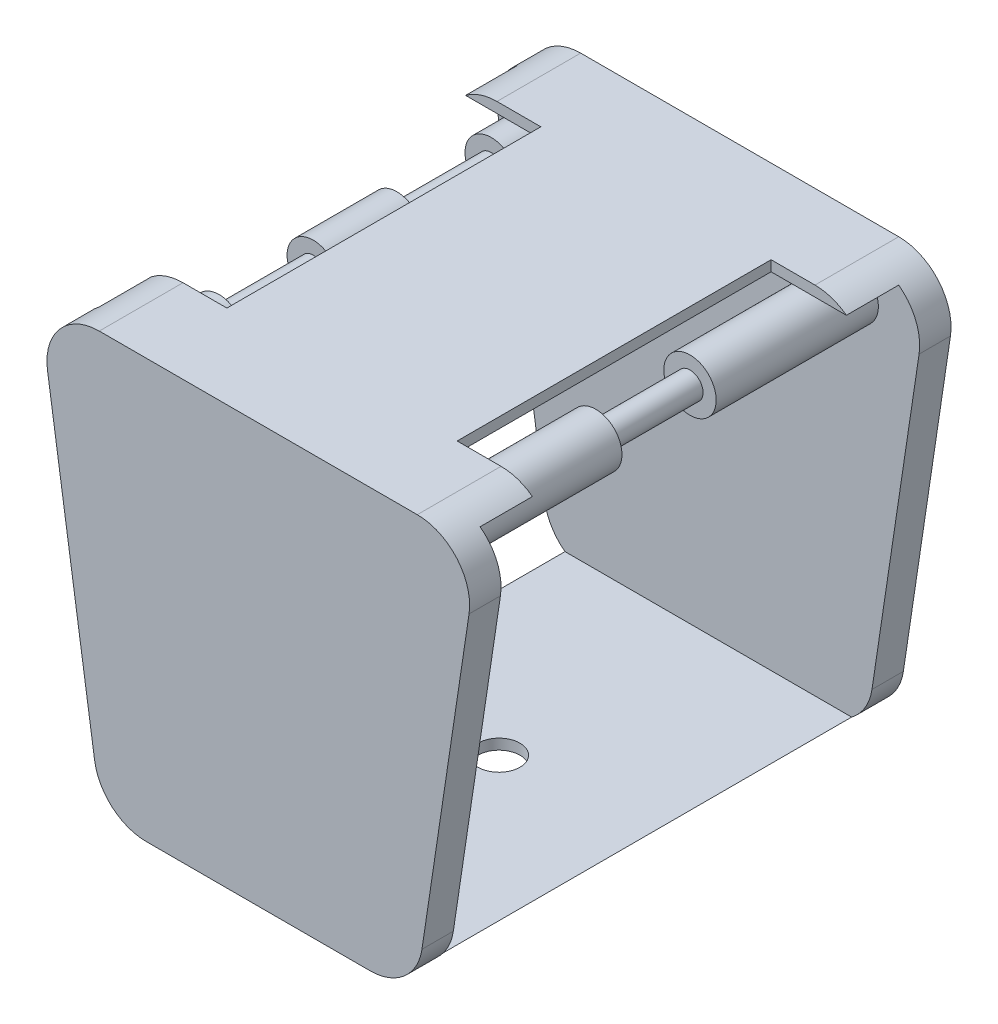
SolidWorks part; units mm, degrees
ref_plane "Front Plane" through (0, 0, 0) normal (0, 0, 1) x (1, 0, 0)
ref_plane "Top Plane" through (0, 0, 0) normal (0, 1, 0) x (1, 0, 0)
ref_plane "Right Plane" through (0, 0, 0) normal (1, 0, 0) x (0, 0, -1)
sketch "Sketch3" plane through (0, 0, 0) normal (0, 0, 1) x (1, 0, 0)
  line L0 (42, 40) -> (-42, 40)
  line L1 (-42, 40) -> (-30, -40)
  line L2 (-30, -40) -> (30, -40)
  line L3 (30, -40) -> (42, 40)
  line L4 (55, 0) -> (-55, 0) construction
  line L5 (0, -55) -> (0, 55) construction
  dimension "D1" = 84
  dimension "D2" = 60
  dimension "D3" = 80
  dimension "D4" = 40
  dimension "D5" = 30
extrude "Boss-Extrude1" add sketch "Sketch3" along normal mid plane 92
sketch "Sketch4" plane through (0, 0, 0) normal (1, 0, 0) x (0, 0, -1)
  line L0 (-46, 40) -> (46, 40) construction
  line L1 (-40, 38) -> (40, 38)
  line L2 (-40, 38) -> (-40, -38)
  line L3 (-40, -38) -> (40, -38)
  line L4 (40, 38) -> (40, -38)
  line L5 (46, -40) -> (46, 40) construction
  dimension "D1" = 80
  dimension "D2" = 76
  dimension "D3" = 2
  dimension "D4" = 6
extrude "Cut-Extrude1" cut sketch "Sketch4" against normal mid plane 92
sketch "Sketch5" plane through (0, 0, 0) normal (0, 0, 1) x (1, 0, 0)
  line L0 (42, 40) -> (-42, 40) construction
  line L1 (0, -44) -> (0, 44) construction
  circle A0 centre (-27.5, 32.5) radius 5
  dimension "D1" = 10
  dimension "D2" = 7.5
  dimension "D3" = 27.5
extrude "Boss-Extrude2" add sketch "Sketch5" along normal mid plane 16 separate body
sketch "Sketch6" plane through (0, 0, 8) normal (0, 0, 1) x (1, 0, 0)
  circle A0 centre (-27.5, 32.5) radius 2.5
  dimension "D1" = 5
extrude "Boss-Extrude3" add sketch "Sketch6" along normal blind 18
sketch "Sketch8" plane through (0, 0, -8) normal (0, 0, -1) x (-1, 0, 0)
  circle A0 centre (27.5, 32.5) radius 2.5
  dimension "D1" = 5
extrude "Boss-Extrude4" add sketch "Sketch8" along normal blind 18
sketch "Sketch9" plane through (0, 0, -26) normal (0, 0, -1) x (-1, 0, 0)
  circle A0 centre (27.5, 32.5) radius 5
  dimension "D1" = 10
extrude "Boss-Extrude5" add sketch "Sketch9" along normal up to surface (14 mm away) up to face at (0, 0, -40)
sketch "Sketch10" plane through (0, 0, 26) normal (0, 0, 1) x (1, 0, 0)
  circle A0 centre (-27.5, 32.5) radius 5
  dimension "D1" = 10
extrude "Boss-Extrude6" add sketch "Sketch10" along normal up to surface (14 mm away) up to face at (0, 0, 40)
sketch "Sketch11" plane through (0, 0, 0) normal (0, 0, 1) x (1, 0, 0)
  line L0 (42, 40) -> (-42, 40) construction
  line L1 (0, -44) -> (0, 44) construction
  circle A0 centre (27.5, 32.5) radius 2.5
  dimension "D1" = 5
  dimension "D2" = 7.5
  dimension "D3" = 27.5
extrude "Boss-Extrude7" add sketch "Sketch11" along normal mid plane 18 separate body
sketch "Sketch12" plane through (0, 0, 9) normal (0, 0, 1) x (1, 0, 0)
  circle A0 centre (27.5, 32.5) radius 5
  dimension "D1" = 10
extrude "Boss-Extrude8" add sketch "Sketch12" along normal up to surface (31 mm away) up to face at (0, 0, 40)
sketch "Sketch13" plane through (0, 0, -9) normal (0, 0, -1) x (-1, 0, 0)
  circle A0 centre (-27.5, 32.5) radius 5
  dimension "D1" = 10
extrude "Boss-Extrude9" add sketch "Sketch13" along normal up to surface (31 mm away) up to face at (0, 0, -40)
sketch "Sketch14" plane through (0, 40, 0) normal (0, 1, 0) x (1, 0, 0)
  line L0 (42, -46) -> (42, 46) construction
  line L1 (22, 30) -> (42, 30)
  line L2 (22, 30) -> (22, -30)
  line L3 (22, -30) -> (42, -30)
  line L4 (42, 30) -> (42, -30)
  line L13 (-42, -46) -> (-42, 46) construction
  line L14 (-42, 30) -> (-22, 30)
  line L15 (-42, 30) -> (-42, -30)
  line L16 (-42, -30) -> (-22, -30)
  line L17 (-22, 30) -> (-22, -30)
  line L18 (42, 46) -> (-42, 46) construction
  dimension "D1" = 20
  dimension "D2" = 60
  dimension "D3" = 60
  dimension "D4" = 16
  dimension "D5" = 20
extrude "Cut-Extrude2" cut sketch "Sketch14" against normal blind 2.2
fillet "Fillet1" radius 10 4 edges at (42, 40, 38) (-42, 40, 38) (-42, 40, -38) (42, 40, -38)
fillet "Fillet2" radius 10 2 edges at (-30, -40, 0) (30, -40, 0)
sketch "Sketch15" plane through (0, -40, 0) normal (0, -1, 0) x (1, 0, 0)
  circle A0 centre (0, 0) radius 4
  dimension "D1" = 8
extrude "Cut-Extrude3" cut sketch "Sketch15" against normal blind 2.2
